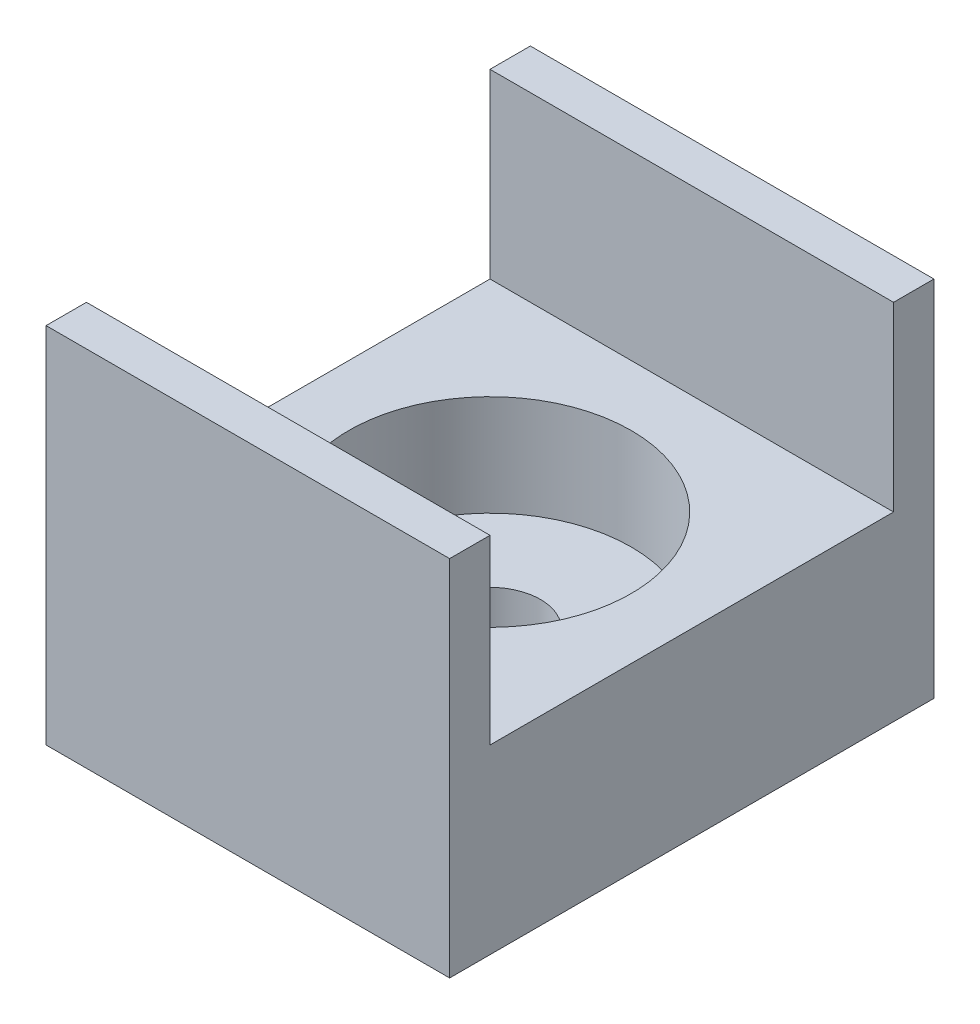
SolidWorks part; units mm, degrees
ref_plane "Front Plane" through (0, 0, 0) normal (0, 0, 1) x (1, 0, 0)
ref_plane "Top Plane" through (0, 0, 0) normal (0, 1, 0) x (1, 0, 0)
ref_plane "Right Plane" through (0, 0, 0) normal (1, 0, 0) x (0, 0, -1)
sketch "Sketch1" plane through (0, 0, 0) normal (1, 0, 0) x (0, 0, -1)
  line L0 (27.94, 22.86) -> (30.48, 22.86)
  line L1 (0, 0) -> (30.48, 0)
  line L2 (0, 0) -> (0, 22.86)
  line L3 (0, 22.86) -> (2.54, 22.86)
  line L4 (30.48, 0) -> (30.48, 22.86)
  line L6 (2.54, 22.86) -> (2.54, 11.43)
  line L7 (2.54, 11.43) -> (27.94, 11.43)
  line L8 (27.94, 22.86) -> (27.94, 11.43)
  point P10 (15.24, 11.43)
  point P11 (15.24, 0)
  dimension "D1" = 30.48
  dimension "D2" = 22.86
  dimension "D3" = 25.4
  dimension "D5" = 11.43
extrude "Boss-Extrude1" add sketch "Sketch1" along normal blind 25.4
sketch "Sketch2" plane through (0, 11.43, 0) normal (0, 1, 0) x (1, 0, 0)
  line L0 (0, 15.24) -> (25.4, 15.24) construction
  line L1 (0, 27.94) -> (0, 2.54) construction
  line L2 (25.4, 27.94) -> (25.4, 2.54) construction
  line L3 (12.7, 0) -> (12.7, 30.48) construction
  line L4 (25.4, 0) -> (0, 0) construction
  line L5 (25.4, 30.48) -> (0, 30.48) construction
  circle A0 centre (12.7, 15.24) radius 3.175
  point P14 (12.7, 15.24)
  dimension "D1" = 6.35
extrude "Cut-Extrude1" cut sketch "Sketch2" against normal through all
sketch "Sketch3" plane through (0, 11.43, 0) normal (0, 1, 0) x (1, 0, 0)
  circle A0 centre (12.7, 15.24) radius 8.89
  dimension "D1" = 17.78
extrude "Cut-Extrude2" cut sketch "Sketch3" against normal offset from surface (6.35 mm away) 5.08 up to face at (12.7, 0, -12.065)
